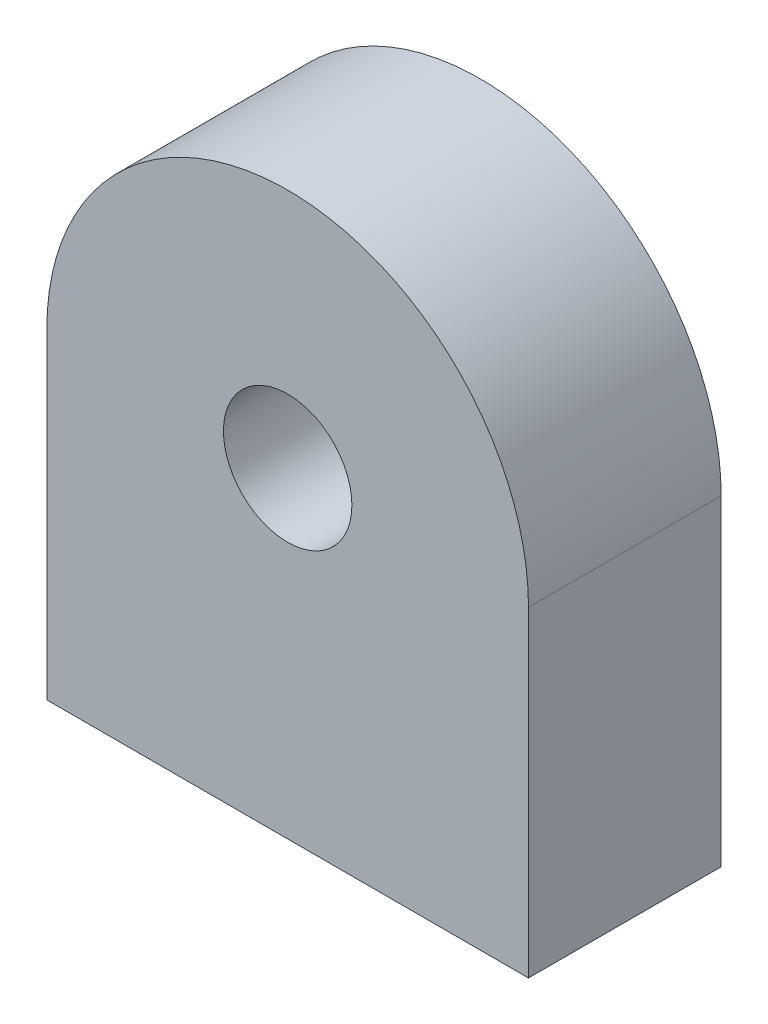
SolidWorks part; units mm, degrees
ref_plane "Alzado" through (0, 0, 0) normal (0, 0, 1) x (1, 0, 0)
ref_plane "Planta" through (0, 0, 0) normal (0, 1, 0) x (1, 0, 0)
ref_plane "Vista lateral" through (0, 0, 0) normal (1, 0, 0) x (0, 0, -1)
sketch "Croquis2" plane through (0, 0, 0) normal (0, 0, 1) x (1, 0, 0)
  line L1 (0, 0) -> (-30, 0)
  line L2 (0, 0) -> (0, 20)
  line L4 (-30, 0) -> (-30, 20)
  arc A0 (0, 20) -> (-30, 20) centre (-15, 20) ccw
  dimension "D1" = 30
  dimension "D2" = 20
extrude "Saliente-Extruir1" add sketch "Croquis2" along normal mid plane 12
sketch "Croquis3" plane through (0, 0, 6) normal (0, 0, 1) x (1, 0, 0)
  circle A0 centre (-15, 20) radius 4
  dimension "D1" = 8
extrude "Cortar-Extruir1" cut sketch "Croquis3" against normal through all
